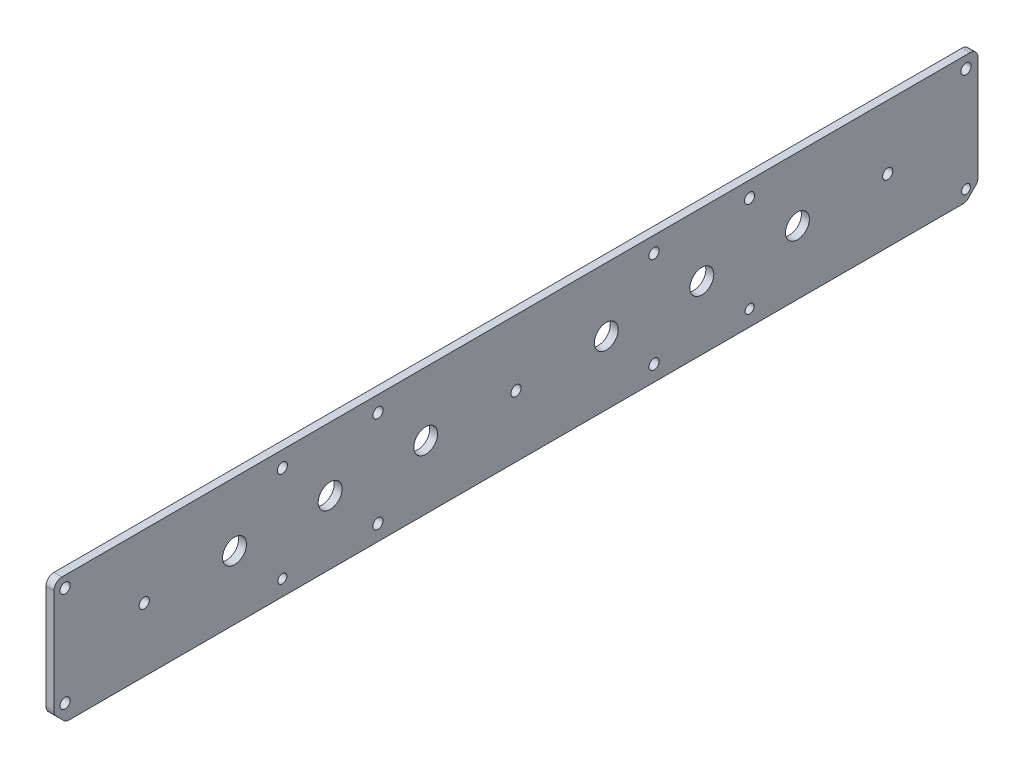
SolidWorks part; units mm, degrees
ref_plane "Front Plane" through (0, 0, 0) normal (0, 0, 1) x (1, 0, 0)
ref_plane "Top Plane" through (0, 0, 0) normal (0, 1, 0) x (1, 0, 0)
ref_plane "Right Plane" through (0, 0, 0) normal (1, 0, 0) x (0, 0, -1)
sketch "Sketch1" plane through (0, 0, 0) normal (1, 0, 0) x (0, 0, -1)
  line L1 (-184.15, -24.6062) -> (184.15, -24.6062)
  line L2 (-184.15, -24.6062) -> (-184.15, 26.1937)
  line L3 (-184.15, 26.1937) -> (184.15, 26.1937)
  line L4 (184.15, -24.6062) -> (184.15, 26.1937)
  point P5 (-180.2907, -26.3795)
  point P6 (0, -24.6062)
  dimension "D1" = 50.8
  dimension "D2" = 368.3
  dimension "D3" = 24.6062
extrude "Boss-Extrude1" add sketch "Sketch1" along normal blind 3.175
chamfer "Chamfer1" distance 4.7625 angle 45 2 edges at (1.5875, -24.6062, -184.15) (1.5875, -24.6062, 184.15)
fillet "Fillet1" radius 3.175 6 edges at (1.5875, -24.6062, -179.3875) (1.5875, -19.8437, -184.15) (1.5875, 26.1937, -184.15) (1.5875, -24.6062, 179.3875) (1.5875, -19.8437, 184.15) (1.5875, 26.1937, 184.15)
sketch "Sketch4" plane through (3.175, 0, 0) normal (1, 0, 0) x (0, 0, -1)
  point P0 (-93.1246, 19.9098)
  point P1 (-55.0246, 19.9098)
  point P3 (0, 0)
  point P5 (55.0246, 19.9098)
  point P7 (93.1246, 19.9098)
  point P9 (55.0246, -18.3223)
  point P11 (-55.0246, -18.3223)
  point P13 (-179.705, 21.7487)
  point P15 (-179.705, -18.0026)
  point P17 (179.3875, 21.4312)
  point P19 (148.1579, 0.7938)
  point P21 (-148.1579, 0.7937)
hole_wizard "#8 Clearance Hole1" positions "Sketch4" profile "Sketch5" hole size "#8" standard "ANSI Inch" end condition up to next
sketch "Sketch5" plane through (3.175, 19.9098, 93.1246) normal (0, 1, 0) x (0, 0, -1)
  line L0 (0, 0) -> (0, 3.175)
  line L1 (0, 3.175) -> (2.032, 3.175)
  line L2 (2.032, 3.175) -> (2.032, 0)
  line L5 (2.032, 0) -> (0, 0)
  line L11 (0, -6.35) -> (0, 107.95) construction
  dimension "Thru Hole Dia." = 4.064
  dimension "Thru Hole Depth" = 3.175
sketch "Sketch6" plane through (3.175, 0, 0) normal (1, 0, 0) x (0, 0, -1)
  point P0 (-93.1246, -18.3223)
  point P1 (93.1246, -18.3223)
  point P3 (179.3875, -20.1161)
hole_wizard "#8 Clearance Hole2" positions "Sketch6" profile "Sketch7" hole size "#8" standard "ANSI Inch" end condition up to next
sketch "Sketch7" plane through (3.175, -18.3223, 93.1246) normal (0, 1, 0) x (0, 0, -1)
  line L0 (0, 0) -> (0, 3.175)
  line L1 (0, 3.175) -> (1.778, 3.175)
  line L2 (1.778, 3.175) -> (1.778, 0)
  line L5 (1.778, 0) -> (0, 0)
  line L11 (0, -6.35) -> (0, 107.95) construction
  dimension "Thru Hole Dia." = 3.556
  dimension "Thru Hole Depth" = 3.175
sketch "Sketch8" plane through (3.175, 0, 0) normal (1, 0, 0) x (0, 0, -1)
  point P0 (-112.1746, 0.7937)
  point P1 (-74.0746, 0.7938)
  point P3 (-35.9746, 0.7938)
  point P5 (35.9746, 0.7938)
  point P7 (74.0746, 0.7937)
  point P9 (112.1746, 0.7937)
hole_wizard "3/8 Clearance Hole1" positions "Sketch8" profile "Sketch9" hole size "3/8" standard "ANSI Inch" end condition up to next
sketch "Sketch9" plane through (3.175, 0.7937, 112.1746) normal (0, 1, 0) x (0, 0, -1)
  line L0 (0, 0) -> (0, 3.175)
  line L1 (0, 3.175) -> (4.7625, 3.175)
  line L2 (4.7625, 3.175) -> (4.7625, 0)
  line L5 (4.7625, 0) -> (0, 0)
  line L11 (0, -6.35) -> (0, 107.95) construction
  dimension "Thru Hole Dia." = 9.525
  dimension "Thru Hole Depth" = 3.175
